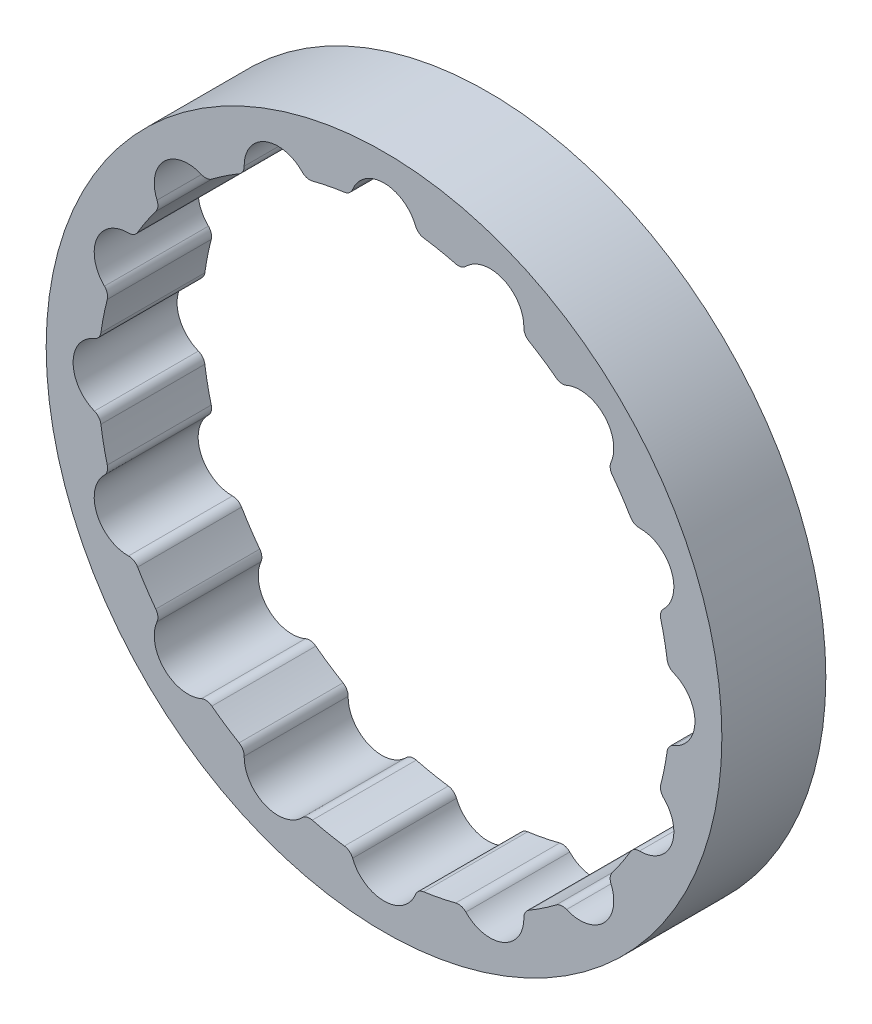
SolidWorks part; units mm, degrees
ref_plane "Front" through (0, 0, 0) normal (0, 0, 1) x (1, 0, 0)
ref_plane "Top" through (0, 0, 0) normal (0, 1, 0) x (1, 0, 0)
ref_plane "Right" through (0, 0, 0) normal (1, 0, 0) x (0, 0, -1)
sketch "Sketch1" plane through (0, 0, 0) normal (0, 0, 1) x (1, 0, 0)
  circle A0 centre (0, 0) radius 32.5
  circle A1 centre (0, 25.4323) radius 1.6772
  arc A2 (-3.1831, 27.3152) -> (3.1831, 27.3152) centre (0, 26.6591) cw
  arc A3 (-3.1831, 27.3152) -> (-7.5123, 26.454) centre (0, 0) ccw
  arc A4 (7.5123, 26.454) -> (13.3939, 24.0178) centre (10.202, 24.6298) cw
  arc A5 (17.0639, 21.5655) -> (21.5655, 17.0639) centre (18.8508, 18.8508) cw
  arc A6 (24.0178, 13.3939) -> (26.454, 7.5123) centre (24.6298, 10.202) cw
  arc A7 (27.3152, 3.1831) -> (27.3152, -3.1831) centre (26.6591, 0) cw
  arc A8 (26.454, -7.5123) -> (24.0178, -13.3939) centre (24.6298, -10.202) cw
  arc A9 (21.5655, -17.0639) -> (17.0639, -21.5655) centre (18.8508, -18.8508) cw
  arc A10 (13.3939, -24.0178) -> (7.5123, -26.454) centre (10.202, -24.6298) cw
  arc A11 (3.1831, -27.3152) -> (-3.1831, -27.3152) centre (0, -26.6591) cw
  arc A12 (-7.5123, -26.454) -> (-13.3939, -24.0178) centre (-10.202, -24.6298) cw
  arc A13 (-17.0639, -21.5655) -> (-21.5655, -17.0639) centre (-18.8508, -18.8508) cw
  arc A14 (-24.0178, -13.3939) -> (-26.454, -7.5123) centre (-24.6298, -10.202) cw
  arc A15 (-27.3152, -3.1831) -> (-27.3152, 3.1831) centre (-26.6591, 0) cw
  arc A16 (-26.454, 7.5123) -> (-24.0178, 13.3939) centre (-24.6298, 10.202) cw
  arc A17 (-21.5655, 17.0639) -> (-17.0639, 21.5655) centre (-18.8508, 18.8508) cw
  arc A18 (-13.3939, 24.0178) -> (-7.5123, 26.454) centre (-10.202, 24.6298) cw
  arc A19 (-13.3939, 24.0178) -> (-17.0639, 21.5655) centre (0, 0) ccw
  arc A20 (-21.5655, 17.0639) -> (-24.0178, 13.3939) centre (0, 0) ccw
  arc A21 (-26.454, 7.5123) -> (-27.3152, 3.1831) centre (0, 0) ccw
  arc A22 (-27.3152, -3.1831) -> (-26.454, -7.5123) centre (0, 0) ccw
  arc A23 (-24.0178, -13.3939) -> (-21.5655, -17.0639) centre (0, 0) ccw
  arc A24 (-17.0639, -21.5655) -> (-13.3939, -24.0178) centre (0, 0) ccw
  arc A25 (-7.5123, -26.454) -> (-3.1831, -27.3152) centre (0, 0) ccw
  arc A26 (3.1831, -27.3152) -> (7.5123, -26.454) centre (0, 0) ccw
  arc A27 (13.3939, -24.0178) -> (17.0639, -21.5655) centre (0, 0) ccw
  arc A28 (21.5655, -17.0639) -> (24.0178, -13.3939) centre (0, 0) ccw
  arc A29 (26.454, -7.5123) -> (27.3152, -3.1831) centre (0, 0) ccw
  arc A30 (27.3152, 3.1831) -> (26.454, 7.5123) centre (0, 0) ccw
  arc A31 (24.0178, 13.3939) -> (21.5655, 17.0639) centre (0, 0) ccw
  arc A32 (17.0639, 21.5655) -> (13.3939, 24.0178) centre (0, 0) ccw
  arc A33 (7.5123, 26.454) -> (3.1831, 27.3152) centre (0, 0) ccw
  point P56 (0, 0)
  dimension "D1" = 65
  dimension "D2" = 55
  dimension "D3" = 3.25
  dimension "D4" = 16
extrude "Boss-Extrude1" add sketch "Sketch1" along normal blind 10 contours A0 A33 A4 A32 A5 A31 A6 A30 A7 A29 A8 A28 A9 A27 A10 A26 A11 A25 A12 A24 A13 A23 A14 A22 A15 A21 A16 A20 A17 A19 A18 A3 A2 region at (-31.5808, 0, 0)
ref_plane "Plane1" through (0, 0, 5) normal (0, 0, 1) x (1, 0, 0)
fillet "Fillet1" radius 1 32 edges at (3.1831, 27.3152, 5) (-3.1831, 27.3152, 5) (-7.5123, 26.454, 5) (-13.3939, 24.0178, 5) (-17.0639, 21.5655, 5) (-21.5655, 17.0639, 5) (-24.0178, 13.3939, 5) (-26.454, 7.5123, 5) (-27.3152, 3.1831, 5) (-26.454, -7.5123, 5) (-24.0178, -13.3939, 5) (-21.5655, -17.0639, 5) (-17.0639, -21.5655, 5) (-13.3939, -24.0178, 5) (-7.5123, -26.454, 5) (-3.1831, -27.3152, 5) (3.1831, -27.3152, 5) (7.5123, -26.454, 5) (13.3939, -24.0178, 5) (17.0639, -21.5655, 5) (21.5655, -17.0639, 5) (24.0178, -13.3939, 5) (26.454, -7.5123, 5) (27.3152, -3.1831, 5) (27.3152, 3.1831, 5) (26.454, 7.5123, 5) (24.0178, 13.3939, 5) (21.5655, 17.0639, 5) (17.0639, 21.5655, 5) (13.3939, 24.0178, 5) (7.5123, 26.454, 5) (-27.3152, -3.1831, 5)
